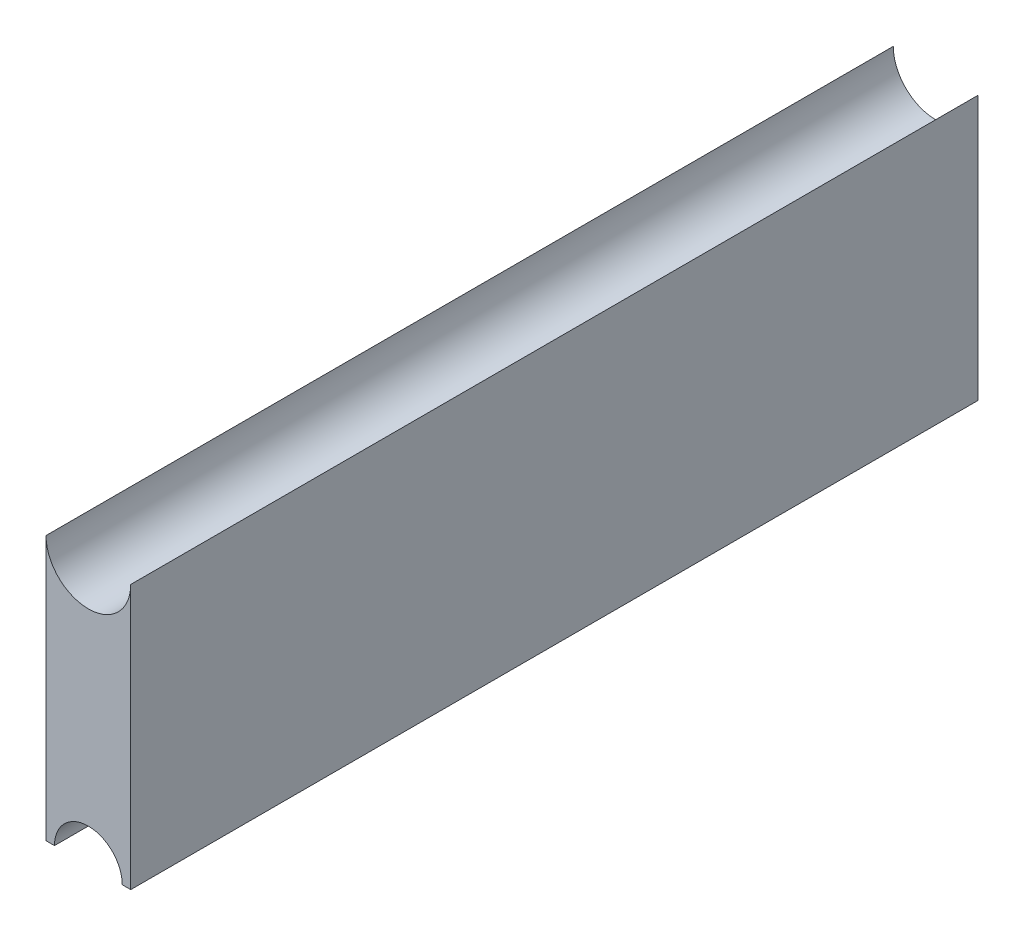
SolidWorks part; units mm, degrees
ref_plane "Front Plane" through (0, 0, 0) normal (0, 0, 1) x (1, 0, 0)
ref_plane "Top Plane" through (0, 0, 0) normal (0, 1, 0) x (1, 0, 0)
ref_plane "Right Plane" through (0, 0, 0) normal (1, 0, 0) x (0, 0, -1)
sketch "Sketch1" plane through (0, 0, 0) normal (0, 0, 1) x (1, 0, 0)
  line L16 (-5.207, -8.382) -> (-11.557, -8.382)
  line L17 (-5.207, -8.382) -> (-5.207, -28.1922)
  line L18 (-11.557, -8.382) -> (-11.557, -28.1922)
  line L19 (-5.207, -28.1922) -> (-11.557, -28.1922)
  circle A0 centre (-8.382, -8.382) radius 3.175
  circle A1 centre (-8.382, -28.194) radius 2.54
  dimension "D9" = 6.35
  dimension "D10" = 5.08
  dimension "D11" = 19.812
extrude "Boss-Extrude4" add sketch "Sketch1" along normal blind 63.5 contours A1 L19 L17 A0 L18 region at (-8.382, -18.7491, 0)
